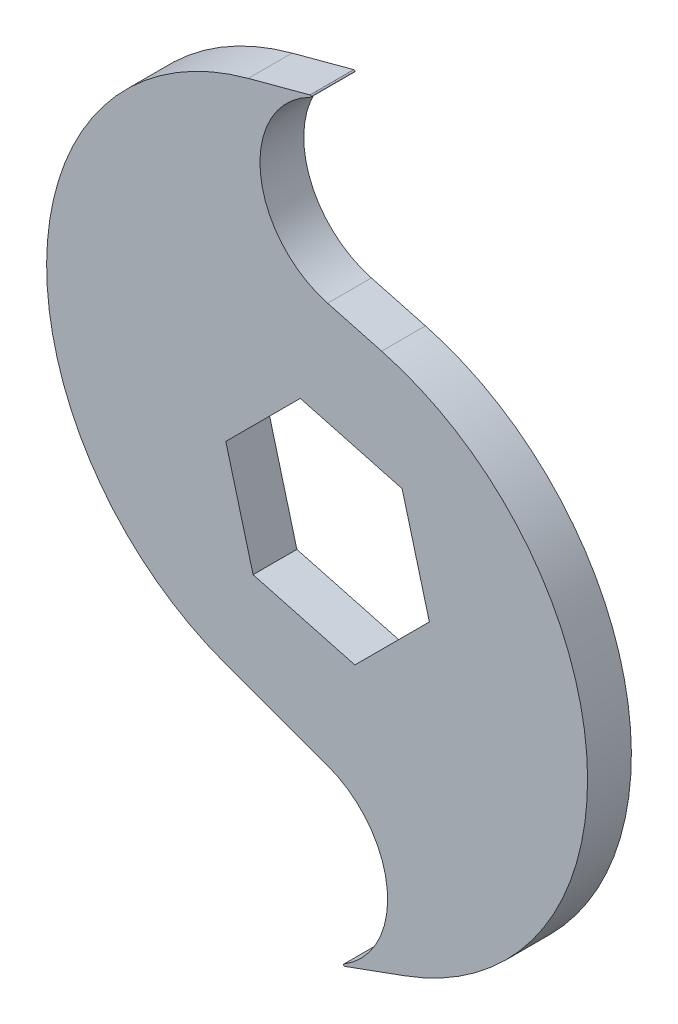
SolidWorks part; units mm, degrees
ref_plane "Front Plane" through (0, 0, 0) normal (0, 0, 1) x (1, 0, 0)
ref_plane "Top Plane" through (0, 0, 0) normal (0, 1, 0) x (1, 0, 0)
ref_plane "Right Plane" through (0, 0, 0) normal (1, 0, 0) x (0, 0, -1)
sketch "Sketch1" plane through (0, 0, 0) normal (0, 0, 1) x (1, 0, 0)
  line L0 (0, 52.07) -> (-11.0405, 49.1117)
  line L1 (0, 52.07) -> (0, 0) construction
  line L2 (0, -52.07) -> (10.7407, -48.1607)
  line L3 (0, 0) -> (0, -52.07) construction
  line L5 (-3.7955, 14.165) -> (-14.165, 3.7955)
  line L6 (-14.165, 3.7955) -> (-10.3695, -10.3695)
  line L7 (-10.3695, -10.3695) -> (3.7955, -14.165)
  line L8 (3.7955, -14.165) -> (14.165, -3.7955)
  line L9 (14.165, -3.7955) -> (10.3695, 10.3695)
  line L10 (10.3695, 10.3695) -> (-3.7955, 14.165)
  line L11 (0, 27.5355) -> (7.5237, 25.5195)
  line L12 (0, -28.2018) -> (-14.1906, -23.0368)
  circle A0 centre (0, 0) radius 52.07 construction
  arc A1 (0, 52.07) -> (0, 27.5355) centre (3.287, 39.8027) ccw
  arc A3 (0, -52.07) -> (0, -28.2018) centre (-4.3437, -40.1359) ccw
  arc A4 (10.7407, -48.1607) -> (7.5237, 25.5195) centre (-2.4834, -11.8278) ccw
  arc A5 (-11.0405, 49.1117) -> (-14.1906, -23.0368) centre (-1.2414, 12.5408) ccw
  circle A6 centre (0, 0) radius 12.7 construction
  dimension "D4" = 70
  dimension "D5" = 25.4
  dimension "D1" = 104.14
  dimension "D6" = 12.7
  dimension "D2" = 11.43
  dimension "D3" = 75
  dimension "D7" = 15
extrude "Boss-Extrude1" add sketch "Sketch1" along normal mid plane 6.096
fillet "Fillet1" radius 0.127 2 edges at (0, 52.07, 0) (0, -52.07, 0)
